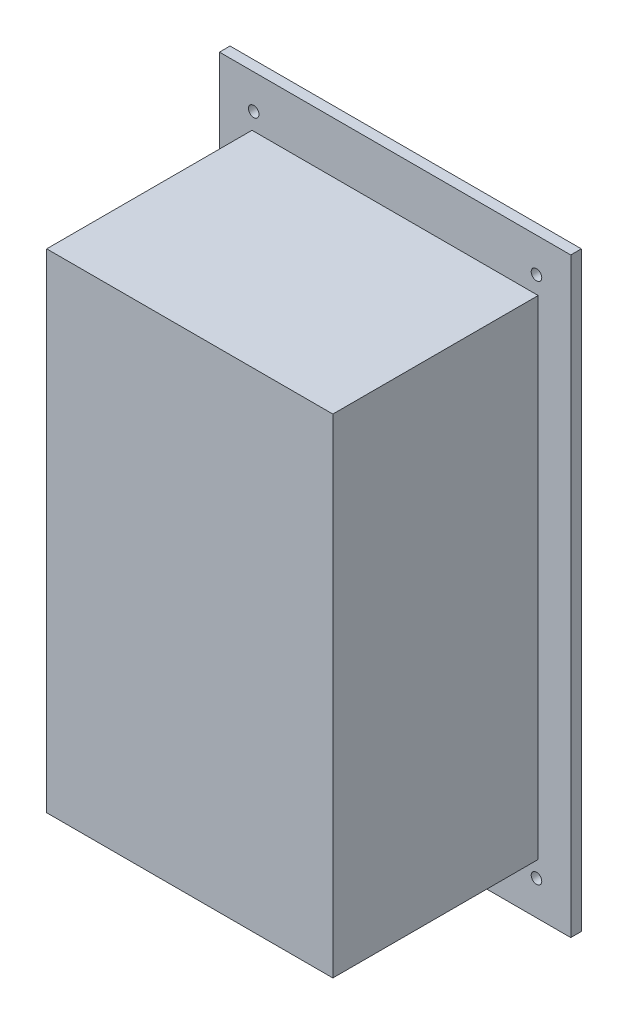
SolidWorks part; units mm, degrees
ref_plane "xy_plane" through (0, 0, 0) normal (0, 0, 1) x (1, 0, 0)
ref_plane "zx_plane" through (0, 0, 0) normal (0, 1, 0) x (1, 0, 0)
ref_plane "yz_plane" through (0, 0, 0) normal (1, 0, 0) x (0, 0, -1)
ref_axis "x_axis" through (-80.9, 0, 0) along (1, 0, 0)
ref_axis "y_axis" through (0, -50, 0) along (0, 1, 0)
ref_axis "z_axis" through (0, 0, -80.9) along (0, 0, 1)
sketch "flange_sketch" plane through (0, 0, 0) normal (0, 0, 1) x (1, 0, 0)
  line L1 (-20.5, 34.5) -> (20.5, 34.5)
  line L2 (-20.5, 34.5) -> (-20.5, -34.5)
  line L3 (-20.5, -34.5) -> (20.5, -34.5)
  line L4 (20.5, 34.5) -> (20.5, -34.5)
  point P4 (-20.5, 0)
  point P5 (0, 34.5)
  point P7 (-88.8332, 140.7693)
  dimension "D1" = 41
  dimension "D2" = 69
sketch "mountHolePositions_sketch" plane through (0, 0, 0) normal (0, 0, 1) x (1, 0, 0)
  line L1 (-16.5, 30.5) -> (16.5, 30.5) construction
  line L2 (-16.5, 30.5) -> (-16.5, -30.5) construction
  line L3 (-16.5, -30.5) -> (16.5, -30.5) construction
  line L4 (16.5, 30.5) -> (16.5, -30.5) construction
  point P0 (0, 0)
  point P4 (0, 30.5)
  point P5 (16.5, 0)
  point P15 (0, 0)
  dimension "D2" = 33
  dimension "D3" = 61
sketch "box_sketch" plane through (0, 0, 0) normal (0, 0, 1) x (1, 0, 0)
  line L1 (-16.7, 28.5) -> (16.7, 28.5)
  line L2 (-16.7, 28.5) -> (-16.7, -28.5)
  line L3 (-16.7, -28.5) -> (16.7, -28.5)
  line L4 (16.7, 28.5) -> (16.7, -28.5)
  point P4 (0, 28.5)
  point P5 (16.7, 0)
  dimension "D1" = 33.4
  dimension "D2" = 57
extrude "box_extrude" add sketch "box_sketch" along normal blind 25.2
extrude "flange_extrude" add sketch "flange_sketch" along normal blind 1.2346
sketch "mountHoles_sketch" plane through (0, 0, 0) normal (0, 0, 1) x (1, 0, 0)
  circle A0 centre (16.5, -30.5) radius 0.6173
  circle A1 centre (16.5, 30.5) radius 0.6173
  circle A2 centre (-16.5, -30.5) radius 0.6173
  circle A3 centre (-16.5, 30.5) radius 0.6173
  point P8 (-67.9631, 8.9704)
  point P9 (0, 0)
  point P11 (0, 0)
  point P13 (0, 0)
  point P15 (0, 0)
  dimension "D1" = 1.2346
extrude "mountHoles_cut" cut sketch "mountHoles_sketch" against normal through all and the other way through all
